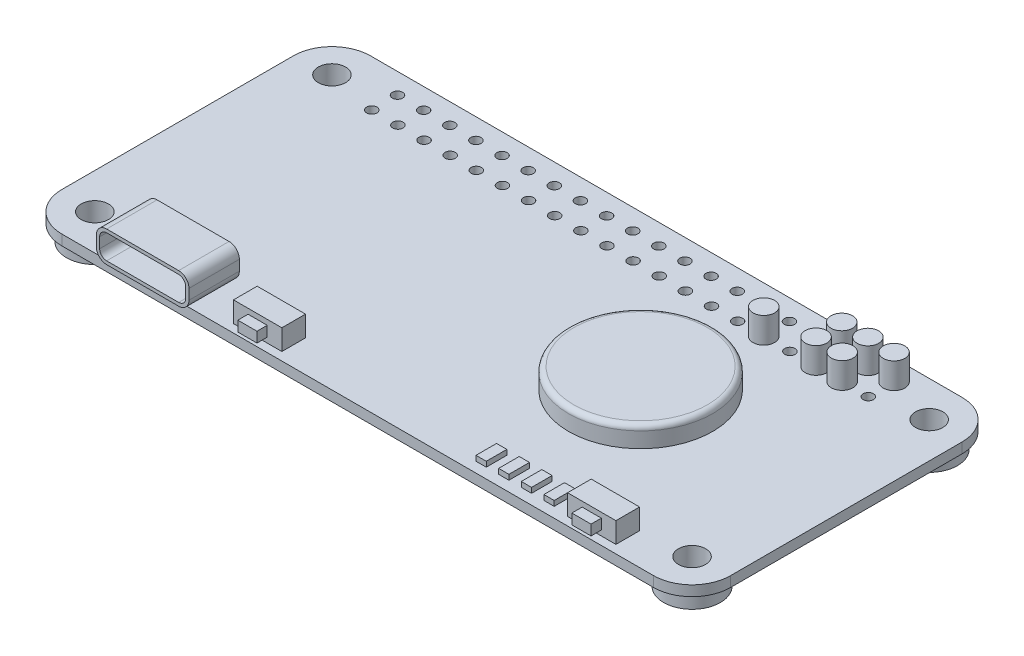
SolidWorks part; units mm, degrees
ref_plane "Front Plane" through (0, 0, 0) normal (0, 0, 1) x (1, 0, 0)
ref_plane "Top Plane" through (0, 0, 0) normal (0, 1, 0) x (1, 0, 0)
ref_plane "Right Plane" through (0, 0, 0) normal (1, 0, 0) x (0, 0, -1)
sketch "Sketch1" plane through (0, 0, 0) normal (0, 1, 0) x (1, 0, 0)
  line L1 (-28.75, 15) -> (28.75, 15)
  line L2 (-32.5, 11.25) -> (-32.5, -11.25)
  line L3 (-28.75, -15) -> (28.75, -15)
  line L4 (32.5, 11.25) -> (32.5, -11.25)
  line L5 (-32.5, 15) -> (32.5, -15) construction
  line L6 (-32.5, -15) -> (32.5, 15) construction
  arc A0 (-32.5, -11.25) -> (-28.75, -15) centre (-28.75, -11.25) ccw
  arc A1 (28.75, -15) -> (32.5, -11.25) centre (28.75, -11.25) ccw
  arc A2 (28.75, 15) -> (32.5, 11.25) centre (28.75, 11.25) cw
  arc A3 (-28.75, 15) -> (-32.5, 11.25) centre (-28.75, 11.25) ccw
  point P0 (0, 0)
  dimension "D3" = 3.75
  dimension "D1" = 65
  dimension "D2" = 30
extrude "Boss-Extrude1" add sketch "Sketch1" along normal blind 1 contours L1 A2 L4 A1 L3 A0 L2 A3
sketch "Sketch2" plane through (0, 1, 0) normal (0, 1, 0) x (1, 0, 0)
  line L0 (0, 15) -> (0, -15) construction
  line L1 (-28.75, 15) -> (28.75, 15) construction
  line L2 (-28.75, -15) -> (28.75, -15) construction
  line L3 (-32.5, 0) -> (32.5, 0) construction
  line L4 (-32.5, 11.25) -> (-32.5, -11.25) construction
  line L5 (32.5, 11.25) -> (32.5, -11.25) construction
  circle A0 centre (-29.025, 11.525) radius 1.325
  circle A2 centre (29.025, 11.525) radius 1.325
  circle A3 centre (29.025, -11.525) radius 1.325
  circle A4 centre (-29.025, -11.525) radius 1.325
  dimension "D1" = 2.65
  dimension "D2" = 2.15
  dimension "D3" = 2.15
extrude "Cut-Extrude1" cut sketch "Sketch2" against normal through all
sketch "Sketch3" plane through (0, 1, 0) normal (0, 1, 0) x (1, 0, 0)
  line L0 (-24.128, 13) -> (-24.128, 10.5) construction
  line L3 (-28.75, 15) -> (28.75, 15) construction
  line L5 (-32.5, 11.25) -> (-32.5, -11.25) construction
  circle A0 centre (-24.128, 13) radius 0.5
  circle A1 centre (-24.128, 10.5) radius 0.5
  dimension "D1" = 1
  dimension "D3" = 1.5
  dimension "D4" = 7.872
  dimension "D2" = 2.5
extrude "Cut-Extrude2" cut sketch "Sketch3" against normal through all
pattern_linear "LPattern1" count 20 spacing 2.54 along (1, 0, 0) of "Cut-Extrude2"
sketch "Sketch15" plane through (0, 0, 15) normal (0, 0, 1) x (1, 0, 0)
  line L0 (-28.75, 1) -> (28.75, 1) construction
  line L2 (-24, 4) -> (-17, 4)
  line L3 (-25, 3) -> (-25, 2)
  line L4 (-24, 1) -> (-17, 1)
  line L5 (-16, 3) -> (-16, 2)
  line L6 (-32.5, 1) -> (-32.5, 0) construction
  line L9 (15.325, 0) -> (15.325, 5.5788) construction
  line L10 (-28.75, 0) -> (28.75, 0) construction
  arc A0 (-17, 4) -> (-16, 3) centre (-17, 3) cw
  arc A1 (-17, 1) -> (-16, 2) centre (-17, 2) ccw
  arc A2 (-25, 2) -> (-24, 1) centre (-24, 2) ccw
  arc A3 (-24, 4) -> (-25, 3) centre (-24, 3) ccw
  point P10 (-16, 4)
  point P13 (-16, 1)
  point P18 (-25, 4)
  dimension "D4" = 1
  dimension "D1" = 9
  dimension "D2" = 3
  dimension "D3" = 7.5
extrude "Boss-Extrude6" add sketch "Sketch15" along normal blind 0.4 and the other way blind 4.5
sketch "Sketch16" plane through (0, 0, 15.4) normal (0, 0, 1) x (1, 0, 0)
  line L4 (-17, 3.68) -> (-24, 3.68)
  line L5 (-17, 3.68) -> (-24, 3.68)
  line L6 (-24.68, 3) -> (-24.68, 2)
  line L7 (-24.68, 3) -> (-24.68, 2)
  line L8 (-24, 1.32) -> (-17, 1.32)
  line L9 (-24, 1.32) -> (-17, 1.32)
  line L10 (-16.32, 2) -> (-16.32, 3)
  line L11 (-16.32, 2) -> (-16.32, 3)
  arc A4 (-16.32, 3) -> (-17, 3.68) centre (-17, 3) ccw
  arc A5 (-16.32, 3) -> (-17, 3.68) centre (-17, 3) ccw
  arc A6 (-24, 3.68) -> (-24.68, 3) centre (-24, 3) ccw
  arc A7 (-24, 3.68) -> (-24.68, 3) centre (-24, 3) ccw
  arc A8 (-24.68, 2) -> (-24, 1.32) centre (-24, 2) ccw
  arc A9 (-24.68, 2) -> (-24, 1.32) centre (-24, 2) ccw
  arc A10 (-17, 1.32) -> (-16.32, 2) centre (-17, 2) ccw
  arc A11 (-17, 1.32) -> (-16.32, 2) centre (-17, 2) ccw
  dimension "D2" = 0.32
extrude "Cut-Extrude9" cut sketch "Sketch16" against normal blind 5.25
sketch "草图1" plane through (0, 1, 0) normal (0, 1, 0) x (1, 0, 0)
  line L1 (-12.87, -11.9) -> (-8.17, -11.9)
  line L2 (-12.87, -11.9) -> (-12.87, -14.2)
  line L3 (-12.87, -14.2) -> (-8.17, -14.2)
  line L4 (-8.17, -11.9) -> (-8.17, -14.2)
  line L5 (-28.75, -15) -> (-24, -15) construction
  line L6 (-16, -10.5) -> (-16, -15.4) construction
  line L7 (32.5, 11.25) -> (32.5, -11.25) construction
  line L8 (24.3, -11.9) -> (19.6, -11.9)
  line L9 (24.3, -11.9) -> (24.3, -14.2)
  line L10 (24.3, -14.2) -> (19.6, -14.2)
  line L11 (19.6, -11.9) -> (19.6, -14.2)
  dimension "D1" = 4.7
  dimension "D2" = 2.3
  dimension "D3" = 3.13
  dimension "D4" = 0.8
  dimension "D5" = 8.2
extrude "凸台-拉伸1" add sketch "草图1" along normal blind 2
sketch "草图2" plane through (0, 0, 14.2) normal (0, 0, 1) x (1, 0, 0)
  line L0 (-12.87, 3) -> (-8.17, 3) construction
  line L5 (-11.45, 2.5) -> (-9.59, 2.5)
  line L6 (-11.45, 2.5) -> (-11.45, 1.5)
  line L7 (-11.45, 1.5) -> (-9.59, 1.5)
  line L8 (-9.59, 2.5) -> (-9.59, 1.5)
  line L9 (-11.45, 2.5) -> (-9.59, 1.5) construction
  line L10 (-11.45, 1.5) -> (-9.59, 2.5) construction
  line L11 (-8.17, 3) -> (-8.17, 1) construction
  line L12 (19.6, 3) -> (24.3, 3) construction
  line L13 (21.02, 2.5) -> (22.88, 2.5)
  line L14 (21.02, 2.5) -> (21.02, 1.5)
  line L15 (21.02, 1.5) -> (22.88, 1.5)
  line L16 (22.88, 2.5) -> (22.88, 1.5)
  line L17 (21.02, 2.5) -> (22.88, 1.5) construction
  line L18 (21.02, 1.5) -> (22.88, 2.5) construction
  line L19 (24.3, 3) -> (24.3, 1) construction
  point P0 (-10.52, 2)
  point P5 (21.95, 2)
  point P8 (-10.52, 3)
  point P12 (-8.17, 2)
  point P19 (21.95, 3)
  point P23 (24.3, 2)
  dimension "D1" = 1.86
  dimension "D2" = 1
extrude "凸台-拉伸2" add sketch "草图2" along normal blind 1
sketch "草图9" plane through (0, 0, 0) normal (0, -1, 0) x (1, 0, 0)
  circle A0 centre (29.025, 11.525) radius 2.75
  circle A1 centre (29.025, -11.525) radius 2.75
  circle A2 centre (-29.025, 11.525) radius 2.75
  circle A3 centre (-29.025, -11.525) radius 2.75
  circle A4 centre (29.025, 11.525) radius 1.325 construction
  circle A5 centre (29.025, -11.525) radius 1.325 construction
  circle A6 centre (-29.025, 11.525) radius 1.325 construction
  circle A7 centre (-29.025, -11.525) radius 1.325 construction
  circle A8 centre (29.025, 11.525) radius 1.325
  circle A9 centre (29.025, -11.525) radius 1.325
  circle A10 centre (-29.025, 11.525) radius 1.325
  circle A11 centre (-29.025, -11.525) radius 1.325
  dimension "D1" = 5.5
extrude "凸台-拉伸8" add sketch "草图9" along normal blind 1.5
sketch "草图10" plane through (0, 1, 0) normal (0, 1, 0) x (1, 0, 0)
  circle A0 centre (24.132, 13) radius 1.05
  circle A1 centre (21.592, 13) radius 1.05
  circle A2 centre (19.052, 13) radius 1.05
  circle A3 centre (21.592, 10.5) radius 1.05
  circle A4 centre (19.052, 10.5) radius 1.05
  circle A6 centre (13.972, 10.5) radius 1.05
extrude "凸台-拉伸9" add sketch "草图10" along normal blind 2.5
sketch "草图11" plane through (0, 1, 0) normal (0, -1, 0) x (1, 0, 0)
  circle A0 centre (24.132, -13) radius 0.5
  circle A1 centre (21.592, -13) radius 0.5
  circle A2 centre (21.592, -10.5) radius 0.5
  circle A3 centre (19.052, -10.5) radius 0.5
  circle A5 centre (19.052, -13) radius 0.5
  circle A8 centre (13.972, -10.5) radius 0.5
extrude "凸台-拉伸10" add sketch "草图11" along normal blind 3
sketch "草图12" plane through (0, 1, 0) normal (0, 1, 0) x (1, 0, 0)
  line L1 (32.5, 11.25) -> (32.5, -11.25) construction
  line L2 (-28.75, 15) -> (28.75, 15) construction
  circle A0 centre (12.5, 0) radius 7
  dimension "D1" = 14
  dimension "D2" = 20
  dimension "D3" = 15
extrude "凸台-拉伸11" add sketch "草图12" along normal blind 2
sketch "草图13" plane through (0, 1, 0) normal (0, 1, 0) x (1, 0, 0)
  line L0 (19.6, -11.9) -> (19.6, -14.2) construction
  line L1 (17.1, -12) -> (18.1, -12)
  line L2 (17.1, -12) -> (17.1, -14)
  line L3 (17.1, -14) -> (18.1, -14)
  line L4 (18.1, -12) -> (18.1, -14)
  line L5 (17.1, -12) -> (18.1, -14) construction
  line L6 (17.1, -14) -> (18.1, -12) construction
  line L7 (14.9, -12) -> (15.9, -12)
  line L8 (14.9, -12) -> (14.9, -14)
  line L9 (14.9, -14) -> (15.9, -14)
  line L10 (15.9, -12) -> (15.9, -14)
  line L11 (14.9, -12) -> (15.9, -14) construction
  line L12 (14.9, -14) -> (15.9, -12) construction
  line L13 (12.7, -12) -> (13.7, -12)
  line L14 (12.7, -12) -> (12.7, -14)
  line L15 (12.7, -14) -> (13.7, -14)
  line L16 (13.7, -12) -> (13.7, -14)
  line L17 (12.7, -12) -> (13.7, -14) construction
  line L18 (12.7, -14) -> (13.7, -12) construction
  line L19 (10.5, -12) -> (11.5, -12)
  line L20 (10.5, -12) -> (10.5, -14)
  line L21 (10.5, -14) -> (11.5, -14)
  line L22 (11.5, -12) -> (11.5, -14)
  line L23 (10.5, -12) -> (11.5, -14) construction
  line L24 (10.5, -14) -> (11.5, -12) construction
  line L25 (-17, -15) -> (28.75, -15) construction
  point P0 (17.6, -13)
  point P5 (15.4, -13)
  point P10 (13.2, -13)
  point P15 (11, -13)
  dimension "D1" = 1
  dimension "D2" = 2
  dimension "D3" = 1.2
  dimension "D4" = 1.2
  dimension "D5" = 1.2
  dimension "D6" = 1.5
  dimension "D7" = 1
extrude "凸台-拉伸12" add sketch "草图13" along normal blind 0.5
fillet "圆角1" radius 0.5 1 edges at (12.5, 3, 7)
sketch "草图14" plane through (0, 0, 10.5) normal (0, 0, -1) x (-1, 0, 0)
  line L4 (16, 3) -> (16, 2)
  line L5 (17, 1) -> (24, 1)
  line L6 (25, 2) -> (25, 3)
  line L7 (24, 4) -> (17, 4)
  line L8 (16, 3) -> (16, 2)
  line L9 (17, 1) -> (24, 1)
  line L10 (25, 2) -> (25, 3)
  line L11 (24, 4) -> (17, 4)
  arc A4 (17, 4) -> (16, 3) centre (17, 3) ccw
  arc A5 (16, 2) -> (17, 1) centre (17, 2) ccw
  arc A6 (24, 1) -> (25, 2) centre (24, 2) ccw
  arc A7 (25, 3) -> (24, 4) centre (24, 3) ccw
  arc A8 (17, 4) -> (16, 3) centre (17, 3) ccw
  arc A9 (16, 2) -> (17, 1) centre (17, 2) ccw
  arc A10 (24, 1) -> (25, 2) centre (24, 2) ccw
  arc A11 (25, 3) -> (24, 4) centre (24, 3) ccw
  dimension "D1" = 0
extrude "凸台-拉伸13" add sketch "草图14" against normal blind 1
